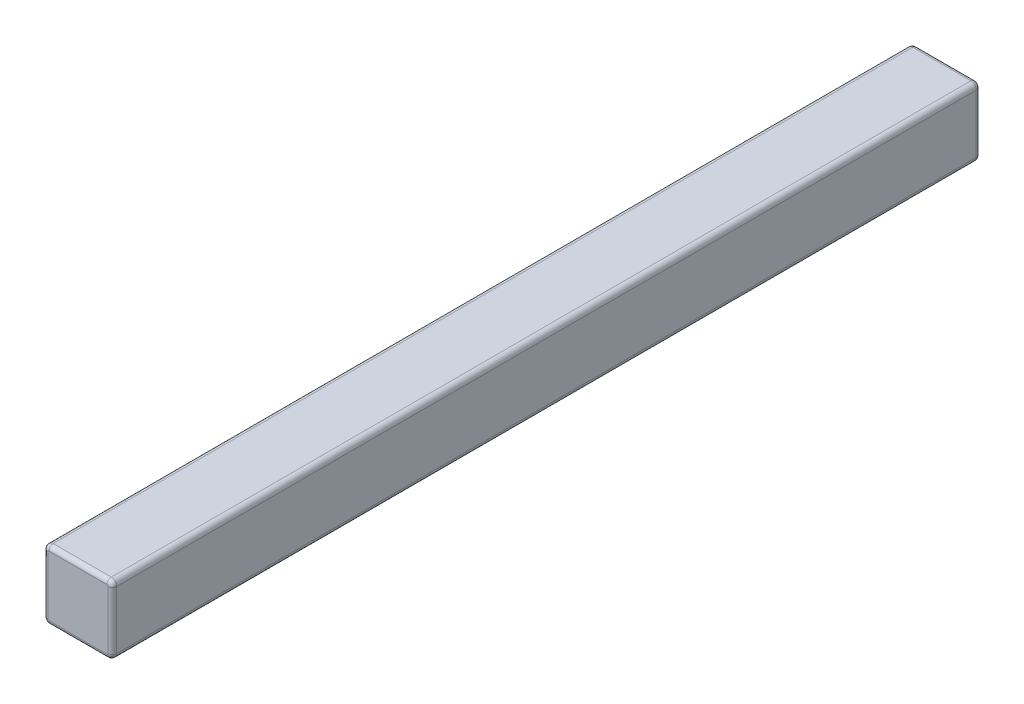
SolidWorks part; units mm, degrees
material "Plain Carbon Steel"
ref_plane "Front Plane" through (0, 0, 0) normal (0, 0, 1) x (1, 0, 0)
ref_plane "Top Plane" through (0, 0, 0) normal (0, 1, 0) x (1, 0, 0)
ref_plane "Right Plane" through (0, 0, 0) normal (1, 0, 0) x (0, 0, -1)
sketch "Sketch1" plane through (0, 0, 0) normal (0, 0, 1) x (1, 0, 0)
  line L1 (-1.3375, 1.5875) -> (1.3375, 1.5875)
  line L2 (-1.5875, 1.3375) -> (-1.5875, -1.3375)
  line L3 (-1.3375, -1.5875) -> (1.3375, -1.5875)
  line L4 (1.5875, 1.3375) -> (1.5875, -1.3375)
  line L5 (-1.5875, 1.5875) -> (1.5875, -1.5875) construction
  line L6 (-1.5875, -1.5875) -> (1.5875, 1.5875) construction
  arc A0 (-1.5875, -1.3375) -> (-1.3375, -1.5875) centre (-1.3375, -1.3375) ccw
  arc A1 (1.3375, -1.5875) -> (1.5875, -1.3375) centre (1.3375, -1.3375) ccw
  arc A2 (1.5875, 1.3375) -> (1.3375, 1.5875) centre (1.3375, 1.3375) ccw
  arc A3 (-1.3375, 1.5875) -> (-1.5875, 1.3375) centre (-1.3375, 1.3375) ccw
  point P0 (0, 0)
  dimension "D2" = 0.25
  dimension "D1" = 3.175
extrude "Boss-Extrude1" add sketch "Sketch1" along normal blind 40 contours L1 A2 L4 A1 L3 A0 L2 A3
fillet "Fillet1" radius 0.2 16 edges at (-1.5875, 0, 0) (-1.5143, -1.5143, 0) (0, -1.5875, 0) (1.5143, -1.5143, 0) (1.5875, 0, 0) (1.5143, 1.5143, 0) (0, 1.5875, 0) (-1.5143, 1.5143, 0) (0, 1.5875, 40) (1.5143, 1.5143, 40) (1.5875, 0, 40) (1.5143, -1.5143, 40) (0, -1.5875, 40) (-1.5143, -1.5143, 40) (-1.5875, 0, 40) (-1.5143, 1.5143, 40)
ref_axis "Axis1" through (0, 0, 0) along (0, 0, 1)
